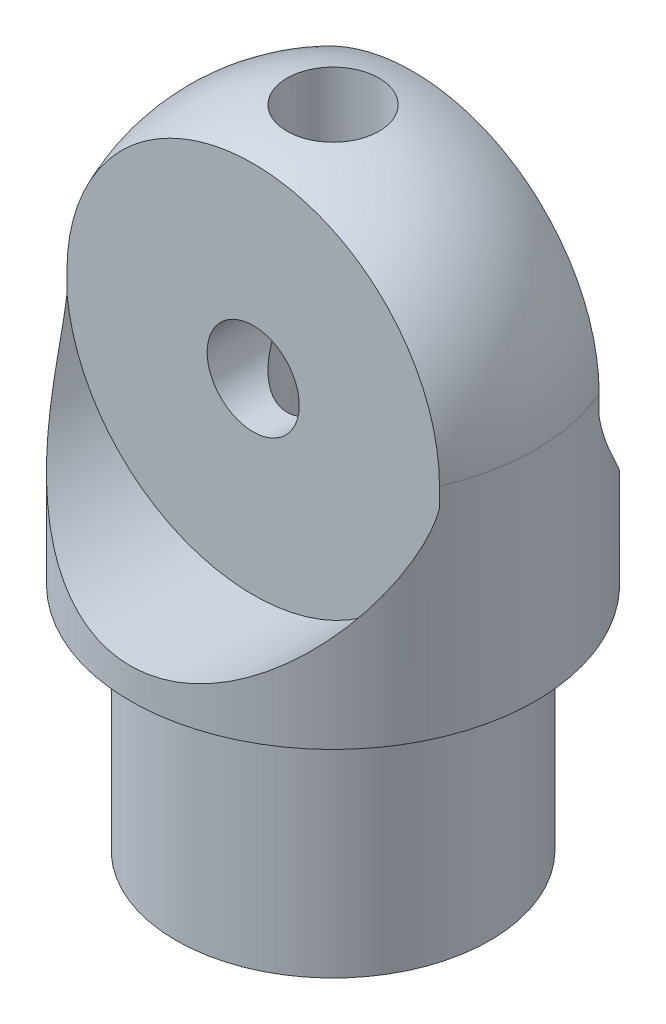
SolidWorks part; units mm, degrees
ref_plane "Front Plane" through (0, 0, 0) normal (0, 0, 1) x (1, 0, 0)
ref_plane "Top Plane" through (0, 0, 0) normal (0, 1, 0) x (1, 0, 0)
ref_plane "Right Plane" through (0, 0, 0) normal (1, 0, 0) x (0, 0, -1)
sketch "Sketch1" plane through (0, 0, 0) normal (0, 1, 0) x (1, 0, 0)
  circle A0 centre (0, 0) radius 12.9794
  dimension "D1" = 25.9588
extrude "Boss-Extrude1" add sketch "Sketch1" along normal blind 19.05
sketch "Sketch2" plane through (0, 0, 0) normal (1, 0, 0) x (0, 0, -1)
  line L0 (0, 55) -> (0, -55) construction
  line L3 (12.9794, 19.05) -> (-12.9794, 19.05) construction
  line L4 (0, 19.05) -> (0, 53.8256)
  line L5 (-16.764, 37.0616) -> (-16.764, 19.05)
  line L6 (-16.764, 19.05) -> (0, 19.05)
  arc A0 (0, 53.8256) -> (-16.764, 37.0616) centre (0, 37.0616) ccw
  dimension "D3" = 33.528
revolve "Revolve1" add sketch "Sketch2" angle 360 about L4
sketch "Sketch4" plane through (0, 0, 0) normal (0, 0, 1) x (1, 0, 0)
  line L0 (16.764, 37.0616) -> (-16.764, 37.0616) construction
  circle A0 centre (0, 37.0616) radius 3.81
  dimension "D1" = 7.62
extrude "Cut-Extrude1" cut sketch "Sketch4" against normal through all both and the other way through all
ref_axis "Axis1" through (0, 37.0616, -16.764) along (0, 0, 1)
ref_plane "Plane1" through (0, 0, -6.604) normal (0, 0, 1) x (1, 0, 0)
sketch "Sketch5" plane through (0, 0, -6.604) normal (0, 0, 1) x (1, 0, 0)
  circle A0 centre (0, 37.0616) radius 15.494
  dimension "D1" = 30.988
extrude "Cut-Extrude2" cut sketch "Sketch5" against normal blind 28.194
mirror "Mirror1" about plane through (0, 0, 0) normal (0, 0, 1) of "Cut-Extrude2"
ref_plane "Plane2" through (0, 27.94, 0) normal (0, 1, 0) x (1, 0, 0)
sketch "Sketch6" plane through (0, 27.94, 0) normal (0, 1, 0) x (1, 0, 0)
  circle A0 centre (0, 0) radius 3.81
  circle A1 centre (0, 0) radius 1.905
extrude "Cut-Extrude3" cut sketch "Sketch6" along normal through all contours A0 A1 | A1 region at (-3.7022, 27.94, 0)
extrude "Cut-Extrude4" cut sketch "Sketch6<3>" against normal through all contours A1 region at (0, 27.94, 0)
sketch "Sketch6<3>" plane through (0, 27.94, 0) normal (0, 1, 0) x (1, 0, 0) same geometry as "Sketch6"
